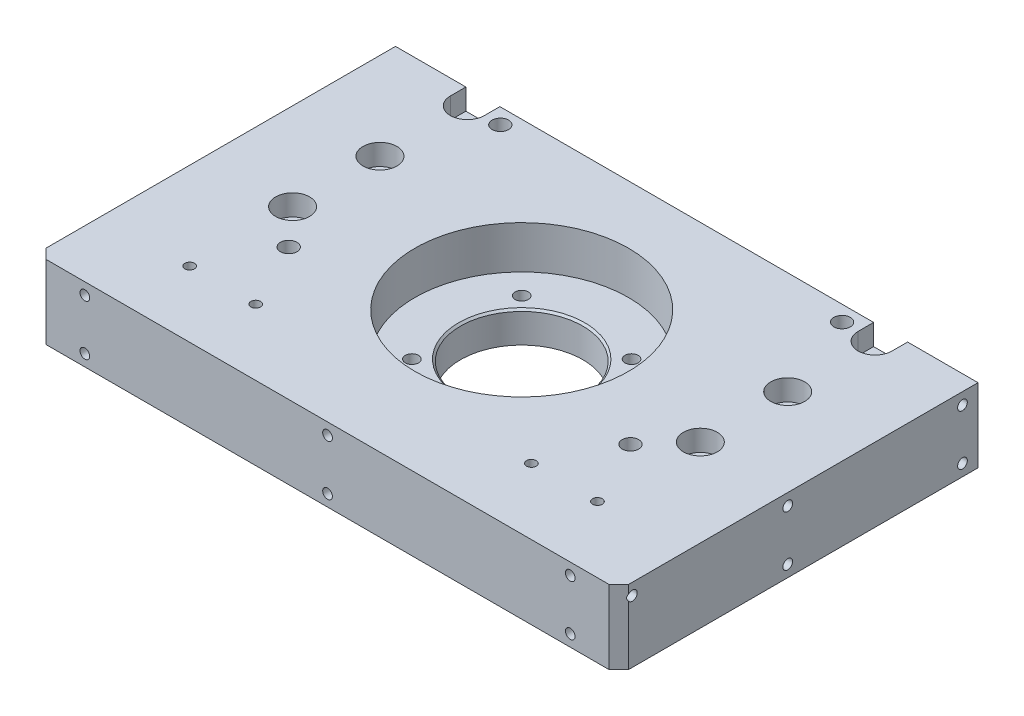
SolidWorks part; units mm, degrees
ref_plane "Front" through (0, 0, 0) normal (0, 0, 1) x (1, 0, 0)
ref_plane "Top" through (0, 0, 0) normal (0, 1, 0) x (1, 0, 0)
ref_plane "Right" through (0, 0, 0) normal (1, 0, 0) x (0, 0, -1)
sketch "Sketch1" plane through (0, 0, 0) normal (0, 1, 0) x (1, 0, 0)
  line L0 (0, -5.4289) -> (0, -230.1993) construction
  line L1 (-150, 0) -> (150, 0)
  line L2 (-150, 0) -> (-150, -185)
  line L3 (-150, -185) -> (150, -185)
  line L4 (150, 0) -> (150, -185)
  dimension "D1" = 300
  dimension "D2" = 185
extrude "Boss-Extrude1" add sketch "Sketch1" along normal blind 38
sketch "Sketch2" plane through (0, 38, 0) normal (0, 1, 0) x (1, 0, 0)
  line L1 (150, 0) -> (-150, 0) construction
  circle A0 centre (0, -85) radius 31.5
  dimension "D1" = 63
  dimension "D2" = 85
extrude "Cut-Extrude1" cut sketch "Sketch2" against normal up to next
sketch "Sketch3" plane through (0, 38, 0) normal (0, 1, 0) x (1, 0, 0)
  circle A0 centre (0, -85) radius 55
  dimension "D1" = 110
extrude "Cut-Extrude2" cut sketch "Sketch3" against normal blind 22
sketch "Sketch6" plane through (0, 38, 0) normal (0, 1, 0) x (1, 0, 0)
  line L0 (0, -7.6651) -> (0, 74.2745) construction
  line L2 (-113.75, -8) -> (-113.75, 0)
  line L3 (-96.25, -8) -> (-96.25, 0)
  line L4 (-96.25, 0) -> (-113.75, 0)
  line L5 (96.25, -8) -> (96.25, 0)
  line L6 (113.75, -8) -> (113.75, 0)
  line L7 (150, 0) -> (-150, 0) construction
  line L8 (113.75, 0) -> (96.25, 0)
  arc A2 (-113.75, -8) -> (-96.25, -8) centre (-105, -8) ccw
  arc A3 (96.25, -8) -> (113.75, -8) centre (105, -8) ccw
  dimension "D4" = 17.5
  dimension "D5" = 8
  dimension "D6" = 210
extrude "Cut-Extrude3" cut sketch "Sketch6" against normal blind 10.8
hole_wizard "CBORE for M10 Socket Head Cap Screw1" positions "Sketch5" profile "Sketch4" counterbore size "M10" standard "JIS" end condition through all
sketch "Sketch5" plane through (0, 38, 0) normal (0, 1, 0) x (-1, 0, 0)
  line L0 (0, 17.088) -> (0, 201.8751) construction
  point P0 (105, 8)
  point P1 (-105, 8)
sketch "Sketch4" plane through (-105, 38, 8) normal (1, 0, 0) x (0, 0, 1)
  line L0 (0, 0) -> (0, 38)
  line L1 (0, 38) -> (6, 38)
  line L3 (6, 38) -> (6, 10.8)
  line L4 (6, 10.8) -> (8.75, 10.8)
  line L5 (8.75, 10.8) -> (8.75, 0)
  line L7 (8.75, 0) -> (0, 0)
  line L11 (0, -6.35) -> (0, 107.95) construction
  dimension "Thru Hole Dia." = 12
  dimension "Thru Hole Depth" = 38
  dimension "C'Bore Dia." = 17.5
  dimension "C'Bore Depth" = 10.8
pattern_linear "LPattern1" count 3 spacing 45 along (0, 0, 1) of "CBORE for M10 Socket Head Cap Screw1"
hole_wizard "M10x1.5 Tapped Hole1" positions "Sketch8" profile "Sketch7" tap size "M10x1.5" standard "JIS"
sketch "Sketch8" plane through (0, 38, 0) normal (0, 1, 0) x (-1, 0, 0)
  line L0 (0, 15.4975) -> (0, 194.6834) construction
  point P0 (88, 8)
  point P1 (-88, 8)
  point P3 (-88, 117)
  point P5 (88, 117)
  dimension "D1" = 109
  dimension "D2" = 176
sketch "Sketch7" plane through (-88, 38, 8) normal (1, 0, 0) x (0, 0, 1)
  line L0 (0, 0) -> (0, 27.0537)
  line L1 (0, 27.0537) -> (4.25, 24.5)
  line L2 (4.25, 24.5) -> (4.25, 0)
  line L5 (4.25, 0) -> (0, 0)
  line L10 (0, 27.0537) -> (-4.25, 24.5) construction
  line L11 (0, -6.35) -> (0, 107.95) construction
  dimension "Tap Drill Dia." = 8.5
  dimension "Tap Drill Depth" = 24.5
  dimension "Drill Angle" = 118
cosmetic thread "Hole Thread1" parameters "D1"=20, "D2"=10
cosmetic thread "Hole Thread2" parameters "D1"=20, "D2"=10
cosmetic thread "Hole Thread21" parameters "D1"=20, "D2"=10
cosmetic thread "Hole Thread22" parameters "D1"=20, "D2"=10
hole_wizard "M10x1.5 Tapped Hole2" positions "Sketch12" profile "Sketch11" tap size "M10x1.5" standard "JIS"
sketch "Sketch12" plane through (0, 0, 0) normal (0, -1, 0) x (1, 0, 0)
  line L0 (0, 11.8825) -> (0, 201.551) construction
  line L4 (96.25, 0) -> (-96.25, 0) construction
  point P0 (25, 174)
  point P1 (-25, 174)
  dimension "D1" = 50
  dimension "D2" = 174
sketch "Sketch11" plane through (25, 0, 174) normal (1, 0, 0) x (0, 0, -1)
  line L0 (0, 0) -> (0, 27.0537)
  line L1 (0, 27.0537) -> (4.25, 24.5)
  line L2 (4.25, 24.5) -> (4.25, 0)
  line L5 (4.25, 0) -> (0, 0)
  line L10 (0, 27.0537) -> (-4.25, 24.5) construction
  line L11 (0, -6.35) -> (0, 107.95) construction
  dimension "Tap Drill Dia." = 8.5
  dimension "Tap Drill Depth" = 24.5
  dimension "Drill Angle" = 118
cosmetic thread "Hole Thread9" parameters "D1"=20, "D2"=10
cosmetic thread "Hole Thread10" parameters "D1"=20, "D2"=10
hole_wizard "M8x1.25 Tapped Hole1" positions "Sketch10" profile "Sketch9" tap size "M8x1.25" standard "JIS" end condition up to next
sketch "Sketch10" plane through (0, 16, 0) normal (0, 1, 0) x (-1, 0, 0)
  line L1 (0, 85) -> (40, 85) construction
  line L4 (0, 85) -> (28.2843, 113.2843) construction
  circle A0 centre (0, 85) radius 40 construction
  point P0 (28.2843, 113.2843)
  point P1 (-28.2843, 113.2843)
  point P3 (-28.2843, 56.7157)
  point P5 (28.2843, 56.7157)
  dimension "D1" = 80
  dimension "D2" = 45
sketch "Sketch9" plane through (-28.2843, 16, 113.2843) normal (1, 0, 0) x (0, 0, 1)
  line L0 (0, 0) -> (0, 16)
  line L1 (0, 16) -> (3.4, 16)
  line L2 (3.4, 16) -> (3.4, 0)
  line L5 (3.4, 0) -> (0, 0)
  line L11 (0, -6.35) -> (0, 107.95) construction
  dimension "Thru Tap Drill Dia." = 6.8
  dimension "Thru Tap Drill Depth" = 16
cosmetic thread "Hole Thread5" parameters "D2"=8
cosmetic thread "Hole Thread6" parameters "D2"=8
cosmetic thread "Hole Thread7" parameters "D2"=8
cosmetic thread "Hole Thread8" parameters "D2"=8
hole_wizard "M6x1.0 Tapped Hole1" positions "Sketch14" profile "Sketch13" tap size "M6x1.0" standard "JIS"
sketch "Sketch14" plane through (0, 38, 0) normal (0, 1, 0) x (-1, 0, 0)
  line L0 (0, 25.7098) -> (0, -213.3126) construction
  line L3 (-150, 0) -> (-113.75, 0) construction
  point P3 (-71, 151)
  point P5 (71, 151)
  point P16 (-105, 151)
  point P18 (105, 151)
  dimension "D1" = 142
  dimension "D2" = 210
  dimension "D3" = 151
sketch "Sketch13" plane through (71, 38, 151) normal (1, 0, 0) x (0, 0, 1)
  line L0 (0, 0) -> (0, 16.5022)
  line L1 (0, 16.5022) -> (2.5, 15)
  line L2 (2.5, 15) -> (2.5, 0)
  line L5 (2.5, 0) -> (0, 0)
  line L10 (0, 16.5022) -> (-2.5, 15) construction
  line L11 (0, -6.35) -> (0, 107.95) construction
  dimension "Tap Drill Dia." = 5
  dimension "Tap Drill Depth" = 15
  dimension "Drill Angle" = 118
cosmetic thread "Hole Thread11" parameters "D1"=15, "D2"=6
cosmetic thread "Hole Thread12" parameters "D1"=15, "D2"=6
cosmetic thread "Hole Thread13" parameters "D1"=15, "D2"=6
cosmetic thread "Hole Thread14" parameters "D1"=15, "D2"=6
hole_wizard "M6x1.0 Tapped Hole2" positions "Sketch16" profile "Sketch15" tap size "M6x1.0" standard "JIS"
sketch "Sketch16" plane through (150, 0, 0) normal (1, 0, 0) x (0, 0, -1)
  line L2 (0, 38) -> (0, 0) construction
  line L3 (-185, 0) -> (0, 0) construction
  point P1 (-8, 6)
  point P3 (-8, 32)
  point P18 (-98, 32)
  point P20 (-98, 6)
  dimension "D1" = 6
  dimension "D2" = 8
  dimension "D3" = 26
  dimension "D4" = 90
sketch "Sketch15" plane through (150, 6, 8) normal (0, 1, 0) x (0, 0, -1)
  line L0 (0, 0) -> (0, 16.5022)
  line L1 (0, 16.5022) -> (2.5, 15)
  line L2 (2.5, 15) -> (2.5, 0)
  line L5 (2.5, 0) -> (0, 0)
  line L10 (0, 16.5022) -> (-2.5, 15) construction
  line L11 (0, -6.35) -> (0, 107.95) construction
  dimension "Tap Drill Dia." = 5
  dimension "Tap Drill Depth" = 15
  dimension "Drill Angle" = 118
cosmetic thread "Hole Thread15" parameters "D1"=12, "D2"=6
cosmetic thread "Hole Thread16" parameters "D1"=12, "D2"=6
cosmetic thread "Hole Thread23" parameters "D1"=12, "D2"=6
cosmetic thread "Hole Thread24" parameters "D1"=12, "D2"=6
hole_wizard "M6x1.0 Tapped Hole4" positions "Sketch18" profile "Sketch17" tap size "M6x1.0" standard "JIS"
sketch "Sketch18" plane through (150, 0, 0) normal (1, 0, 0) x (0, 0, -1)
  point P0 (-178, 32)
  dimension "D1" = 80
sketch "Sketch17" plane through (150, 32, 178) normal (0, 1, 0) x (0, 0, -1)
  line L0 (0, 0) -> (0, 16.5022)
  line L1 (0, 16.5022) -> (2.5, 15)
  line L2 (2.5, 15) -> (2.5, 0)
  line L5 (2.5, 0) -> (0, 0)
  line L10 (0, 16.5022) -> (-2.5, 15) construction
  line L11 (0, -6.35) -> (0, 107.95) construction
  dimension "Tap Drill Dia." = 5
  dimension "Tap Drill Depth" = 15
  dimension "Drill Angle" = 118
cosmetic thread "Hole Thread25" parameters "D1"=12, "D2"=6
mirror "Mirror1" about plane through (0, 0, 0) normal (1, 0, 0) of "M6x1.0 Tapped Hole4", "M6x1.0 Tapped Hole2"
hole_wizard "M6x1.0 Tapped Hole3" positions "Sketch20" profile "Sketch19" tap size "M6x1.0" standard "JIS"
sketch "Sketch20" plane through (92.0342, -6.6492, 185) normal (0, 0, -1) x (-1, 0, 0)
  line L0 (92.0342, -8.263) -> (92.0342, 51.6854) construction
  line L2 (-57.9658, 6.6492) -> (242.0342, 6.6492) construction
  point P0 (-32.9658, 12.6492)
  point P1 (92.0342, 12.6492)
  point P3 (217.0342, 12.6492)
  dimension "D1" = 250
  dimension "D2" = 6
sketch "Sketch19" plane through (125, 6, 185) normal (1, 0, 0) x (0, -1, 0)
  line L0 (0, 0) -> (0, 16.5022)
  line L1 (0, 16.5022) -> (2.5, 15)
  line L2 (2.5, 15) -> (2.5, 0)
  line L5 (2.5, 0) -> (0, 0)
  line L10 (0, 16.5022) -> (-2.5, 15) construction
  line L11 (0, -6.35) -> (0, 107.95) construction
  dimension "Tap Drill Dia." = 5
  dimension "Tap Drill Depth" = 15
  dimension "Drill Angle" = 118
cosmetic thread "Hole Thread18" parameters "D1"=12, "D2"=6
cosmetic thread "Hole Thread19" parameters "D1"=12, "D2"=6
cosmetic thread "Hole Thread20" parameters "D1"=12, "D2"=6
pattern_linear "LPattern3" count 2 spacing 26 along (0, 1, 0) of "M6x1.0 Tapped Hole3"
chamfer "Chamfer1" distance 5 angle 45 2 edges at (150, 19, 185) (-150, 19, 185)
chamfer "Chamfer2" distance 1 angle 45 1 edges at (0, 16, 116.5)
